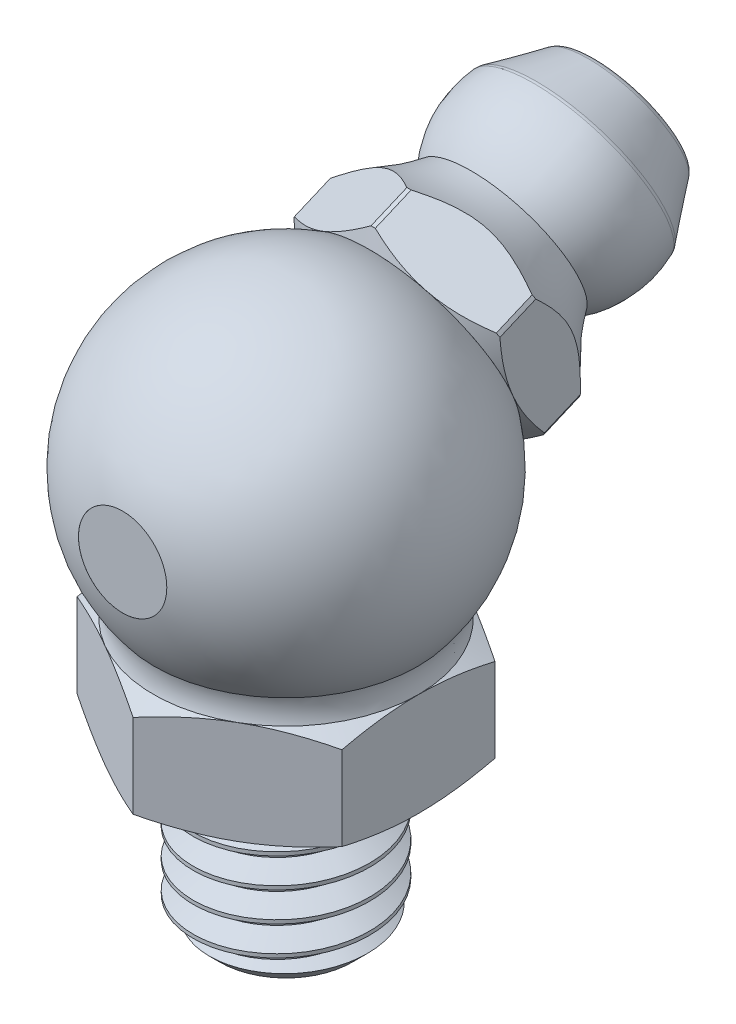
SolidWorks part; units mm, degrees
ref_plane "Front Plane" through (0, 0, 0) normal (0, 0, 1) x (1, 0, 0)
ref_plane "Top Plane" through (0, 0, 0) normal (0, 1, 0) x (1, 0, 0)
ref_plane "Right Plane" through (0, 0, 0) normal (1, 0, 0) x (0, 0, -1)
sketch "Sketch1" plane through (0, 0, 0) normal (1, 0, 0) x (0, 0, -1)
  line L0 (0, -9.5869) -> (0, 9.5869) construction
  line L1 (-3, -4.0869) -> (3, -4.0869) construction
  line L2 (4.5, -4.0869) -> (-4.5, -4.0869) construction
  line L3 (-3, -4.0869) -> (-3, -5.0869) construction
  line L4 (0, 3.8369) -> (12.2, 9.0155) construction
  line L5 (8.3527, 10.9131) -> (10.8925, 4.9298) construction
  line L6 (12.2, -9.5869) -> (12.2, 12.0145) construction
  circle A0 centre (0, 3.8369) radius 5.75 construction
  point P0 (0, -4.0869)
  point P3 (-5.75, 3.8369)
  point P4 (0, 0)
  point P8 (0, -4.0869)
  point P12 (0, -4.0869)
  point P15 (0, -0.5869)
  point P19 (12.2, 9.0155)
  point P20 (-3, -8.5869)
  point P22 (9.6226, 7.9215)
  dimension "Head Diameter" = 11.5
  dimension "Thread Size" = 6
  dimension "Thread Length" = 5.5
  dimension "Shank Length" = 5.5
  dimension "Hex Size" = 9
  dimension "Thread Pitch" = 1
  dimension "Hex Height" = 3.5
  dimension "D1" = 1
  dimension "Nipple Angle" = 67
  dimension "Nipple Diameter" = 6.5
  dimension "Centerline to End of Nipple" = 12.2
  dimension "Nipple Dia. Offset" = 2.8
  dimension "Overall Height" = 20.5
ref_plane "Plane1" through (0, 9.0155, 0) normal (0, 1, 0) x (1, 0, 0)
sketch "Sketch5" plane through (0, 0, 0) normal (1, 0, 0) x (0, 0, -1)
  line L0 (0, 9.5869) -> (0, -1.9131)
  arc A0 (0, -1.9131) -> (0, 9.5869) centre (0, 3.8369) ccw
revolve "Revolve2" add sketch "Sketch5" angle 360 about L0
sketch "Sketch6" plane through (0, 0, 0) normal (1, 0, 0) x (0, 0, -1)
  line L0 (0, 0) -> (0, 9.5869) construction
  line L1 (0, 3.8369) -> (9.9334, 8.0534) construction
  line L2 (3.8058, 9.5869) -> (2.5153, 9.5869)
  line L3 (3.8058, 9.5869) -> (6.78, 2.5803)
  line L4 (6.78, 2.5803) -> (5.4894, 2.5803)
  line L5 (2.5153, 9.5869) -> (5.4894, 2.5803)
  circle A0 centre (0, 3.8369) radius 5.75 construction
  point P8 (5.567, 2.3977)
  point P14 (2.8319, 8.8412)
  point P16 (5.2929, 6.0836)
  dimension "D1" = 7
  dimension "D2" = 67
extrude "Cut-Extrude1" cut sketch "Sketch6" against normal through all both and the other way through all
sketch "Sketch8" plane through (0, 0, 0) normal (0, 1, 0) x (1, 0, 0)
  circle A0 centre (0, 0) radius 3
  dimension "D1" = 6
extrude "Boss-Extrude3" add sketch "Sketch8" along normal up to vertex (-4.0869 mm away) from vertex separate body up to point (0, -4.0869, 0) starting at point (0, -9.5869, 0)
ref_plane "Plane5" through (0, 95.9131, 0) normal (0, 1, 0) x (1, 0, 0)
sketch "Sketch9" plane through (0, -4.0869, 0) normal (0, 1, 0) x (1, 0, 0)
  line L1 (4.5, -2.5981) -> (4.5, 2.5981)
  line L2 (4.5, 2.5981) -> (0, 5.1962)
  line L3 (0, 5.1962) -> (-4.5, 2.5981)
  line L4 (-4.5, 2.5981) -> (-4.5, -2.5981)
  line L5 (-4.5, -2.5981) -> (0, -5.1962)
  line L6 (0, -5.1962) -> (4.5, -2.5981)
  circle A0 centre (0, 0) radius 4.5 construction
  dimension "D1" = 9
extrude "Boss-Extrude4" add sketch "Sketch9" along normal blind 3.5
ref_plane "Plane2" through (0, -2.3369, 0) normal (0, 1, 0) x (1, 0, 0)
sketch "Sketch13" plane through (0, -0.5869, 0) normal (0, 1, 0) x (1, 0, 0)
  line L0 (-4.5, 2.5981) -> (-4.5, -2.5981) construction
  circle A0 centre (0, 0) radius 4.5
extrude "Cut-Extrude2" cut sketch "Sketch13" against normal through all draft 65 flip side to cut
mirror "Mirror1" about plane through (0, -2.3369, 0) normal (0, 1, 0) of "Cut-Extrude2"
sketch "Sketch10" plane through (0, -0.5869, 0) normal (0, 1, 0) x (1, 0, 0)
  line L0 (0, 4.5) -> (0, -4.5) construction
  line L1 (0, 5.1962) -> (-4.5, 2.5981) construction
  circle A0 centre (0, 0) radius 4.5
sketch "Sketch12" plane through (0, 0, 0) normal (1, 0, 0) x (0, 0, -1)
  line L0 (4.5, -0.5869) -> (-4.5, -0.5869) construction
  line L1 (-4.5, -0.5869) -> (0, -0.5869)
  line L2 (0, -9.5869) -> (0, 9.5869) construction
  line L5 (-5.1962, -0.5869) -> (-2.5981, -0.5869) construction
  line L6 (0, -9.5869) -> (0, 3.8369) construction
  line L7 (-4.9796, 0.9619) -> (0, 0.9619)
  line L8 (0, 0.9619) -> (0, -0.5869)
  arc A2 (-4.5, -0.5869) -> (-4.9796, 0.9619) centre (-5.8066, -0.1429) ccw
  circle A3 centre (0, 3.8369) radius 5.75 construction
  dimension "D2" = 1.38
  dimension "D1" = 2.875
revolve "Revolve4" add sketch "Sketch12" angle 360 about L0
chamfer "Chamfer1" distance 0.75 angle 45 1 edges at (0, -9.5869, 3)
ref_plane "Plane6" through (0, -4.0869, 0) normal (0, -1, 0) x (-1, 0, 0)
ref_plane "Plane4" through (0, 0, 5.75) normal (0, 0, 1) x (1, 0, 0)
sketch "Sketch66" plane through (0, 0, 5.75) normal (0, 0, 1) x (1, 0, 0)
  circle A0 centre (0, 3.8369) radius 1.5
  arc A2 (4.4779, 0.2298) -> (-4.4779, 0.2298) centre (0, 3.8369) ccw construction
  dimension "D1" = 3
extrude "Cut-Extrude6" cut sketch "Sketch66" against normal blind 0.2
sketch "Sketch69" plane through (0, 0, 0) normal (1, 0, 0) x (0, 0, -1)
  line L9 (5.7623, 1.9374) -> (4.1994, 5.6195)
  line L14 (12.2, 6.5712) -> (10.051, 11.634) construction
  line L21 (0, 3.8369) -> (12.2, 9.0155) construction
  line L24 (4.1994, 5.6195) -> (11.3209, 8.6423)
  line L29 (11.3209, 8.6423) -> (12.2, 6.5712)
  line L30 (12.2, -9.5869) -> (12.2, 12.0145) construction
  line L31 (12.2, 6.5712) -> (10.9964, 4.9739)
  line L32 (5.7623, 1.9374) -> (7.3034, 2.5916)
  line L33 (5.4894, 2.5803) -> (2.8319, 8.8412) construction
  arc A8 (10.9964, 4.9739) -> (8.3905, 4.4698) centre (9.1299, 7.6345) cw
  arc A9 (8.3905, 4.4698) -> (7.3034, 2.5916) centre (13.0421, 0.5236) ccw
  point P27 (9.7473, 4.4437)
  dimension "D2" = 2
  dimension "D3" = 3.25
  dimension "D10" = 3.25
  dimension "D6" = 6.1
  dimension "D7" = 2.6959
  dimension "D1" = 120
  dimension "D5" = 2.25
  dimension "D8" = 4
  dimension "D9" = 1.6741
  dimension "Nipple OD" = 5.5
revolve "Revolve5" add sketch "Sketch69" angle 360 about L24
sketch "Sketch70" plane through (0, 2.3683, -5.5794) normal (0, -0.3907, 0.9205) x (1, 0, 0)
  line L1 (3.5, 1.5112) -> (3.5, 5.5526)
  line L2 (3.5, 5.5526) -> (0, 7.5733)
  line L3 (0, 7.5733) -> (-3.5, 5.5526)
  line L4 (-3.5, 5.5526) -> (-3.5, 1.5112)
  line L5 (-3.5, 1.5112) -> (0, -0.5096)
  line L6 (0, -0.5096) -> (3.5, 1.5112)
  circle A0 centre (0, 3.5319) radius 3.5 construction
  dimension "D1" = 7
extrude "Cut-Extrude7" cut sketch "Sketch70" against normal through all flip side to cut
sketch "Sketch71" plane through (0, 2.3683, -5.5794) normal (0, -0.3907, 0.9205) x (1, 0, 0)
  line L0 (3.4271, 5.5947) -> (0.0729, 7.5312) construction
  line L1 (-0.0729, 7.5312) -> (-3.4271, 5.5947) construction
  line L2 (-3.4271, 1.469) -> (-0.0729, -0.4674) construction
  circle A0 centre (0, 3.5319) radius 3.5
extrude "Cut-Extrude8" cut sketch "Sketch71" against normal through all draft 55 flip side to cut
sketch "Sketch72" plane through (0, 0, 0) normal (1, 0, 0) x (0, 0, -1)
  line L0 (0, 3.8369) -> (12.2, 9.0155) construction
  line L1 (0, -9.5869) -> (0, 9.5869) construction
  line L2 (1.8278, 4.6128) -> (12.2, 9.0155)
  line L3 (0, -9.5869) -> (0, 1.8513)
  arc A0 (1.8278, 4.6128) -> (0, 1.8513) centre (3, 1.8513) ccw
  dimension "D1" = 3
sweep "Cut-Sweep2" cut path "Sketch72" circular profile diameter 2.5 parameters "D3"=2.5
sketch "Sketch85" plane through (0, 0, 0) normal (1, 0, 0) x (0, 0, -1)
  line L0 (10.8324, 9.793) -> (3.711, 6.7701) construction
  line L2 (4.6878, 4.4688) -> (11.8093, 7.4917) construction
  line L4 (11.8093, 7.4917) -> (10.8324, 9.793) construction
  line L5 (4.1994, 5.6195) -> (11.3209, 8.6423) construction
  line L6 (9.0196, 7.6655) -> (11.3209, 8.6423)
  arc A0 (9.0196, 7.6655) -> (11.3209, 8.6423) centre (10.1702, 8.1539) ccw
revolve "Revolve6" add sketch "Sketch85" angle 360 about L5
sketch "Sketch86" plane through (0, 0, 0) normal (1, 0, 0) x (0, 0, -1)
  point P0 (3, -8.8369)
  point P1 (2.25, -9.5869)
fillet "Fillet1" radius 0.3 2 edges at (0, 6.5712, -12.2) (0, 4.9739, -10.9964)
sketch "Sketch67" plane through (0, -9.5869, 0) normal (0, -1, 0) x (1, 0, 0)
  circle A0 centre (0, 0) radius 3 construction
  circle A1 centre (0, 0) radius 3
curve "Helix/Spiral1" pitch 1 height 6.5 radius 3 centre (0, -9.5869, 0) axis (0, 1, 0) start towards (0, 0, 1)
sketch "Sketch68" plane through (0, 0, 0) normal (1, 0, 0) x (0, 0, -1)
  line L0 (-3, -9.5869) -> (-3, -10.4619)
  line L1 (-3, -10.4619) -> (-2.3505, -10.0869)
  line L2 (-2.3505, -9.9619) -> (-3, -9.5869)
  line L3 (-2.3505, -10.0869) -> (-2.3505, -9.9619)
  line L4 (-2.3505, -10.0244) -> (-3, -10.0244) construction
  line L5 (-2.6752, -10.2744) -> (-2.6752, -9.7744) construction
  point P11 (-2.6752, -10.0244)
  dimension "D1" = 60
  dimension "D2" = 0.125
  dimension "D3" = 0.5
sweep "Cut-Sweep1" cut profiles "Sketch68" path "Helix/Spiral1"
equation "\"D1@Sketch8\"=\"Thread Size@Sketch1\""
equation "\"D1@Sketch9\"=\"Hex Size@Sketch1\""
equation "\"D1@Boss-Extrude4\"=\"Hex Height@Sketch1\""
equation "\"D1@Chamfer1\"=\"Thread Pitch@Sketch1\"*.75"
equation "\"D4@Helix/Spiral1\"=\"Thread Pitch@Sketch1\""
equation "\"D3@Helix/Spiral1\"=\"Thread Length@Sketch1\"+\"Thread Pitch@Sketch1\""
equation "\"D2@Sketch68\"=\"Thread Pitch@Sketch1\"/8"
equation "\"D3@Sketch68\"=\"Thread Pitch@Sketch1\"/2"
equation "\"D1@Sketch12\"=\"Head Diameter@Sketch1\"*.25"
equation "\"D2@Sketch12\"     = \"Head Diameter@Sketch1\"*.12"
equation "\"D1@Sketch1\"=\"Thread Pitch@Sketch1\""
equation "\"D2@Sketch6\"=\"Nipple Angle@Sketch1\""
